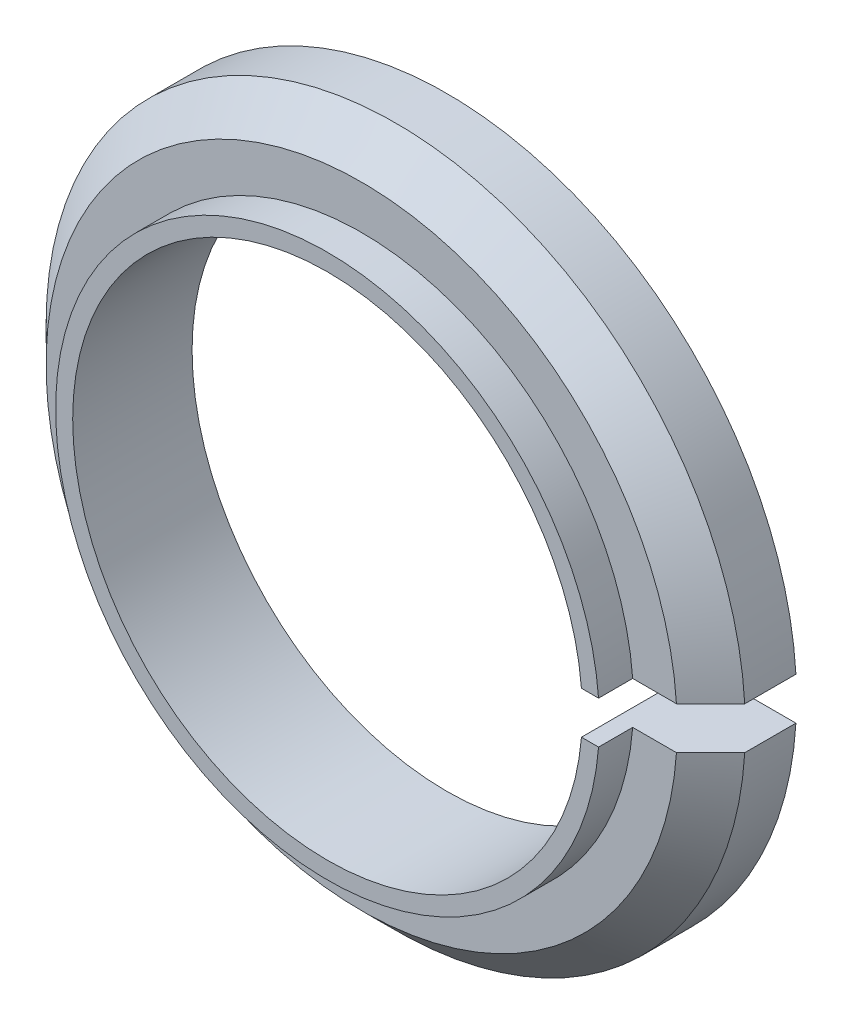
SolidWorks part; units mm, degrees
ref_plane "Front Plane" through (0, 0, 0) normal (0, 0, 1) x (1, 0, 0)
ref_plane "Top Plane" through (0, 0, 0) normal (0, 1, 0) x (1, 0, 0)
ref_plane "Right Plane" through (0, 0, 0) normal (1, 0, 0) x (0, 0, -1)
sketch "Sketch1" plane through (0, 0, 0) normal (0, 0, 1) x (1, 0, 0)
  circle A0 centre (0, 0) radius 14.94
  circle A1 centre (0, 0) radius 20.5
  circle A2 centre (0, 0) radius 15.94
  dimension "D1" = 29.88
  dimension "D2" = 41
  dimension "D3" = 1
extrude "Boss-Extrude1" add sketch "Sketch1" along normal blind 7 contours A2 A0 region at (-15.4891, 0, 0)
extrude "Boss-Extrude2" add sketch "Sketch1<3>" along normal blind 5 contours A1 A2 region at (-19.9202, 0, 0)
sketch "Sketch1<3>" plane through (0, 0, 0) normal (0, 0, 1) x (1, 0, 0) same geometry as "Sketch1"
chamfer "Chamfer1" distance 2 angle 45 1 edges at (20.5, 0, 5)
ref_plane "Plane1" through (20.5, 0, 0) normal (1, 0, 0) x (0, 0, -1)
sketch "Sketch2" plane through (20.5, 0, 0) normal (1, 0, 0) x (0, 0, -1)
  line L0 (-3, -20.5) -> (-3, 20.5) construction
  line L1 (-7, 1.2412) -> (1, 1.2412)
  line L2 (-7, 1.2412) -> (-7, -1.2412)
  line L3 (-7, -1.2412) -> (1, -1.2412)
  line L4 (1, 1.2412) -> (1, -1.2412)
  line L5 (-7, 1.2412) -> (1, -1.2412) construction
  line L6 (-7, -1.2412) -> (1, 1.2412) construction
  line L7 (-7, 15.94) -> (-7, -15.94) construction
  point P0 (-3, 0)
  dimension "D1" = 1.2412
extrude "Cut-Extrude1" cut sketch "Sketch2" against normal blind 13
